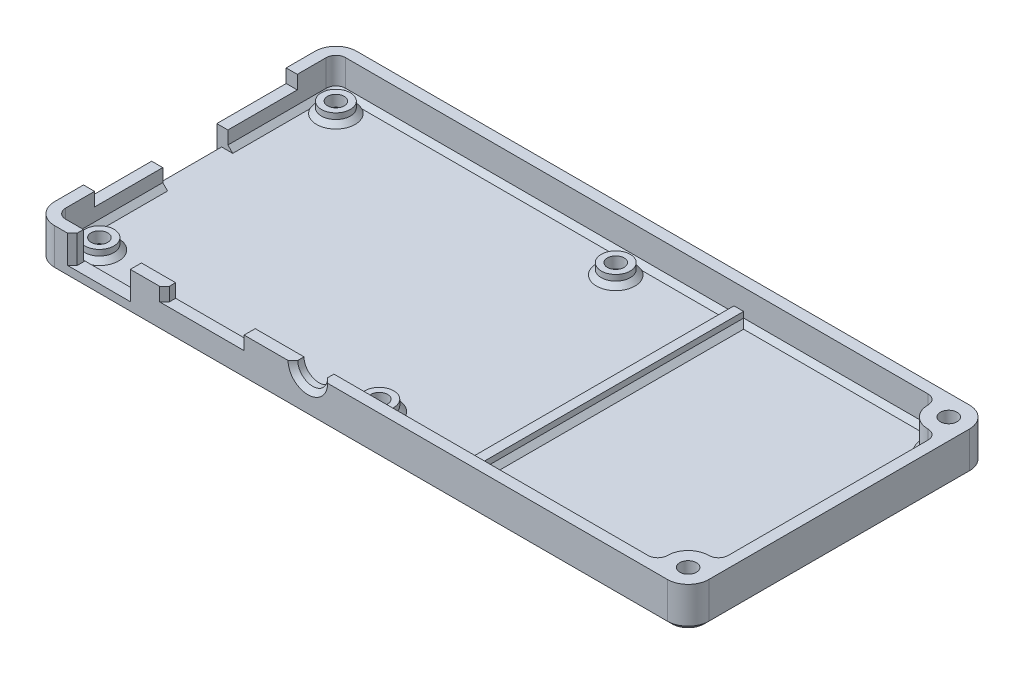
SolidWorks part; units mm, degrees
ref_plane "Front Plane" through (0, 0, 0) normal (0, 0, 1) x (1, 0, 0)
ref_plane "Top Plane" through (0, 0, 0) normal (0, 1, 0) x (1, 0, 0)
ref_plane "Right Plane" through (0, 0, 0) normal (1, 0, 0) x (0, 0, -1)
sketch "Sketch1" plane through (0, 0, 0) normal (0, 1, 0) x (1, 0, 0)
  line L0 (-71.5618, 3.106) -> (57.4382, 3.106) construction
  line L1 (-71.5618, 31.106) -> (57.4382, 31.106)
  line L2 (-71.5618, 31.106) -> (-71.5618, -24.894)
  line L3 (-71.5618, -24.894) -> (57.4382, -24.894)
  line L4 (57.4382, 31.106) -> (57.4382, -24.894)
  line L5 (-60.6618, -24.894) -> (-60.6618, -31.6828) construction
  line L6 (-68.0618, 27.606) -> (-10.0618, 27.606)
  line L7 (-68.0618, 27.606) -> (-68.0618, -21.394)
  line L8 (-68.0618, -21.394) -> (-10.0618, -21.394)
  line L9 (-10.0618, 27.606) -> (-10.0618, -21.394)
  line L10 (-39.5618, -24.894) -> (-39.5618, -31.6828) construction
  line L11 (-18.0618, -24.894) -> (-18.0618, -31.6828) construction
  line L12 (-65.4118, -26.5648) -> (-55.9118, -26.5648) construction
  line L13 (-48.0618, -26.5648) -> (-31.0618, -26.5648) construction
  line L14 (-22.0618, -26.5648) -> (-14.0618, -26.5648) construction
  line L15 (-72.5618, 9.606) -> (-72.5618, -3.394) construction
  line L16 (-71.5618, 3.106) -> (-72.5618, 3.106) construction
  dimension "D1" = 129
  dimension "D2" = 56
  dimension "D3" = 49
  dimension "D4" = 58
  dimension "D5" = 3.5
  dimension "D6" = 3.5
  dimension "D7" = 10.9
  dimension "D8" = 32
  dimension "D9" = 53.5
  dimension "D10" = 2
  dimension "D11" = 13
  dimension "D12" = 9.5
  dimension "D13" = 17
  dimension "D14" = 8
sketch "Sketch3" plane through (0, 0, 0) normal (0, 1, 0) x (1, 0, 0)
  line L4 (60.7382, 34.406) -> (-74.8618, 34.406)
  line L5 (-74.8618, 34.406) -> (-74.8618, -28.194)
  line L6 (-74.8618, -28.194) -> (60.7382, -28.194)
  line L7 (60.7382, -28.194) -> (60.7382, 34.406)
  line L8 (58.4382, 32.106) -> (-72.5618, 32.106)
  line L9 (58.4382, -25.894) -> (58.4382, 32.106)
  line L10 (-72.5618, -25.894) -> (58.4382, -25.894)
  line L11 (-72.5618, 32.106) -> (-72.5618, -25.894)
  line L12 (58.4382, 32.106) -> (-72.5618, 32.106)
  line L13 (58.4382, -25.894) -> (58.4382, 32.106)
  line L14 (-72.5618, -25.894) -> (58.4382, -25.894)
  line L15 (-72.5618, 32.106) -> (-72.5618, -25.894)
  line L16 (-7.0618, 3.106) -> (-7.0618, 34.406) construction
  line L17 (-71.5618, 3.106) -> (57.4382, 3.106) construction
  line L20 (-74.8618, 3.106) -> (52.7382, 3.106) construction
  line L25 (60.7382, -28.194) -> (60.7382, 34.406) construction
  line L26 (58.4382, -25.894) -> (58.4382, 32.106) construction
  dimension "D1" = 1
  dimension "D2" = 2.3
extrude "Boss-Extrude1" add sketch "Sketch3" along normal blind 8.5
sketch "Sketch5" plane through (0, 0, 0) normal (0, 1, 0) x (1, 0, 0)
  line L1 (-72.5618, 32.106) -> (58.4382, 32.106)
  line L2 (-72.5618, 32.106) -> (-72.5618, -25.894)
  line L3 (-72.5618, -25.894) -> (58.4382, -25.894)
  line L4 (58.4382, 32.106) -> (58.4382, -25.894)
extrude "Boss-Extrude2" add sketch "Sketch5" along normal blind 2
sketch "Sketch6" plane through (0, 2, 0) normal (0, 1, 0) x (1, 0, 0)
  circle A0 centre (-68.0618, 27.606) radius 3
  circle A1 centre (-68.0618, -21.394) radius 3
  circle A2 centre (-10.0618, -21.394) radius 3
  circle A3 centre (-10.0618, 27.606) radius 3
extrude "Boss-Extrude3" add sketch "Sketch6" along normal blind 2.2
sketch "Sketch10" plane through (0, 2, 0) normal (0, 1, 0) x (1, 0, 0)
  line L0 (58.4382, 32.106) -> (-72.5618, 32.106) construction
  line L1 (9.9382, 32.106) -> (11.9382, 32.106)
  line L2 (9.9382, 32.106) -> (9.9382, -25.894)
  line L3 (9.9382, -25.894) -> (11.9382, -25.894)
  line L4 (11.9382, 32.106) -> (11.9382, -25.894)
  line L5 (-72.5618, -25.894) -> (58.4382, -25.894) construction
  line L6 (-10.0618, 27.606) -> (-10.0618, -21.394) construction
  dimension "D1" = 2
  dimension "D2" = 20
extrude "Boss-Extrude4" add sketch "Sketch10" along normal blind 2.2
sketch "Sketch11" plane through (0, 0, 28.194) normal (0, 0, 1) x (1, 0, 0)
  line L0 (-74.8618, 8.5) -> (-74.8618, 0) construction
  line L1 (-66.8618, 8.5) -> (-54.8618, 8.5)
  line L2 (-66.8618, 8.5) -> (-66.8618, 2.7)
  line L3 (-66.8618, 2.7) -> (-54.8618, 2.7)
  line L4 (-54.8618, 8.5) -> (-54.8618, 2.7)
  line L5 (-74.8618, 0) -> (60.7382, 0) construction
  line L6 (-60.8618, 8.5) -> (-60.6618, 0) construction
  line L7 (-65.4118, 0) -> (-55.9118, 0) construction
  line L9 (-47.778, 8.5) -> (-31.278, 8.5)
  line L10 (-47.778, 8.5) -> (-47.778, 5.7)
  line L11 (-47.778, 5.7) -> (-31.278, 5.7)
  line L12 (-31.278, 8.5) -> (-31.278, 5.7)
  line L13 (-68.0618, 0) -> (-10.0618, 0) construction
  line L14 (-39.5618, 0) -> (-39.528, 8.5) construction
  line L15 (-48.0618, 0) -> (-31.0618, 0) construction
  line L16 (-18.0618, 0) -> (-18.0618, 8.5) construction
  line L17 (-22.0618, 0) -> (-14.0618, 0) construction
  line L18 (-74.8618, 8.5) -> (60.7382, 8.5) construction
  circle A0 centre (-18.0618, 8.5) radius 3.1
  dimension "D5" = 6.2
  dimension "D1" = 2.7
  dimension "D2" = 12
  dimension "D3" = 5.7
  dimension "D4" = 16.5
  dimension "D6" = 8
  dimension "D7" = 5.8
  dimension "D8" = 2.8
extrude "Cut-Extrude1" cut sketch "Sketch11" against normal up to next
sketch "Sketch12" plane through (-74.8618, 0, 0) normal (-1, 0, 0) x (0, 0, 1)
  line L0 (-3.106, 0) -> (-3.106, 8.5) construction
  line L1 (-27.606, 0) -> (21.394, 0) construction
  line L2 (-34.406, 8.5) -> (28.194, 8.5) construction
  line L3 (-24.106, 5.7) -> (17.894, 5.7)
  line L4 (-9.7329, 5.7) -> (3.7671, 5.7)
  line L5 (-9.7329, 5.7) -> (-9.7329, 2)
  line L6 (-9.7329, 2) -> (3.7671, 2)
  line L7 (3.7671, 5.7) -> (3.7671, 2)
  line L8 (-24.106, 8.5) -> (17.894, 8.5)
  line L9 (-24.106, 8.5) -> (-24.106, 5.7)
  line L10 (-34.406, 0) -> (28.194, 0) construction
  line L11 (17.894, 8.5) -> (17.894, 5.7)
  line L12 (-9.7329, 3.85) -> (3.7671, 3.85) construction
  point P17 (-3.106, 5.7)
  dimension "D1" = 13.5
  dimension "D2" = 5.7
  dimension "D3" = 3.7
  dimension "D4" = 2
extrude "Cut-Extrude2" cut sketch "Sketch12" against normal up to next contours L9 L3 L11 L8 | L7 L6 L5 L4
fillet "Fillet6" radius 2 1 edges at (58.4382, 5.25, -32.106)
fillet "Fillet8" radius 2 2 edges at (-72.5618, 5.25, 25.894) (-72.5618, 5.25, -32.106)
chamfer "Chamfer1" distance 1 angle 45 4 edges at (-68.0618, 2, 24.394) (-10.0618, 2, 24.394) (-10.0618, 2, -24.606) (-68.0618, 2, -24.606)
sketch "Sketch24" plane through (0, 2, 0) normal (0, 1, 0) x (1, 0, 0)
  line L0 (11.9382, 3.106) -> (61.5789, 3.106) construction
  line L1 (11.9382, -25.894) -> (11.9382, 32.106) construction
  line L2 (60.7382, -28.194) -> (60.7382, 34.406) construction
  circle A0 centre (56.4382, -23.894) radius 4.3
  circle A1 centre (56.4382, 30.106) radius 4.3
  dimension "D1" = 4.3
extrude "Boss-Extrude7" add sketch "Sketch24" along normal up to surface (6.5 mm away) up to face at (-8.3784, 8.5, -11.175)
fillet "Fillet21" radius 2 1 edges at (52.6317, 5.25, 25.894)
fillet "Fillet22" radius 2 3 edges at (58.4382, 5.25, 20.0874) (58.4382, 5.25, -26.2994) (52.6317, 5.25, -32.106)
fillet "Fillet20" radius 4.3 4 edges at (60.7382, 4.25, 28.194) (-74.8618, 4.25, -34.406) (-74.8618, 4.25, 28.194) (60.7382, 4.25, -34.406)
chamfer "Chamfer5" distance 1 angle 45 17 edges at (-72.5618, 2, 13.8305) (-72.5618, 2, -19.9195) (-71.976, 2, 25.3082) (-71.976, 2, -31.5202) (-30.3118, 2, 25.894) (-30.3118, 2, -32.106) (9.9382, 2, -3.106) (11.9382, 2, -3.106) (31.0382, 2, -32.106) (31.0382, 2, 25.894) (53.3977, 2, 20.8534) (58.4382, 2, -3.106) (53.3977, 2, -27.0654) (51.5524, 2, 25.3082) (57.8524, 2, 19.0082) (57.8524, 2, -25.2202) (51.5524, 2, -31.5202)
hole_wizard "CSK for #4 Flat Head Socket Cap Screw1" positions "Sketch28" profile "Sketch27" countersink size "#4" standard "ANSI Inch"
sketch "Sketch28" plane through (0, 0, 0) normal (0, -1, 0) x (-1, 0, 0)
  point P0 (68.0618, 27.606)
  point P4 (68.0618, -21.394)
  point P8 (-56.4382, 30.106)
  point P12 (-56.4382, -23.894)
  point P15 (10.0618, -21.394)
  point P19 (10.0618, 27.606)
sketch "Sketch27" plane through (-68.0618, 0, -27.606) normal (1, 0, 0) x (0, 0, -1)
  line L0 (0, 0) -> (0, 15.0378)
  line L1 (0, 15.0378) -> (1.7272, 14)
  line L2 (1.7272, 14) -> (1.7272, 1.8805)
  line L3 (1.7272, 1.8805) -> (3.3619, 0)
  line L5 (3.3619, 0) -> (0, 0)
  line L6 (-1.7272, 1.8805) -> (-3.3619, 0) construction
  line L10 (0, 15.0378) -> (-1.7272, 14) construction
  line L11 (0, -6.35) -> (0, 107.95) construction
  dimension "Hole Dia." = 3.4544
  dimension "Hole Depth" = 14
  dimension "Near C'Sink Dia." = 6.7238
  dimension "Near C'Sink Angle" = 82
  dimension "Drill Angle" = 118
chamfer "Chamfer6" distance 1 angle 45 3 edges at (-18.0618, 5.4, 28.194) (-47.778, 7.1, 28.194) (-66.8618, 5.6, 28.194)
chamfer "Chamfer7" distance 1 angle 45 8 edges at (-74.8618, 0, -3.106) (-73.6023, 0, 26.9346) (-73.6023, 0, -33.1466) (-7.0618, 0, 28.194) (-7.0618, 0, -34.406) (59.4788, 0, 26.9346) (59.4788, 0, -33.1466) (60.7382, 0, -3.106)
chamfer "Chamfer8" distance 1 angle 45 1 edges at (-74.8618, 2, -2.9829)
